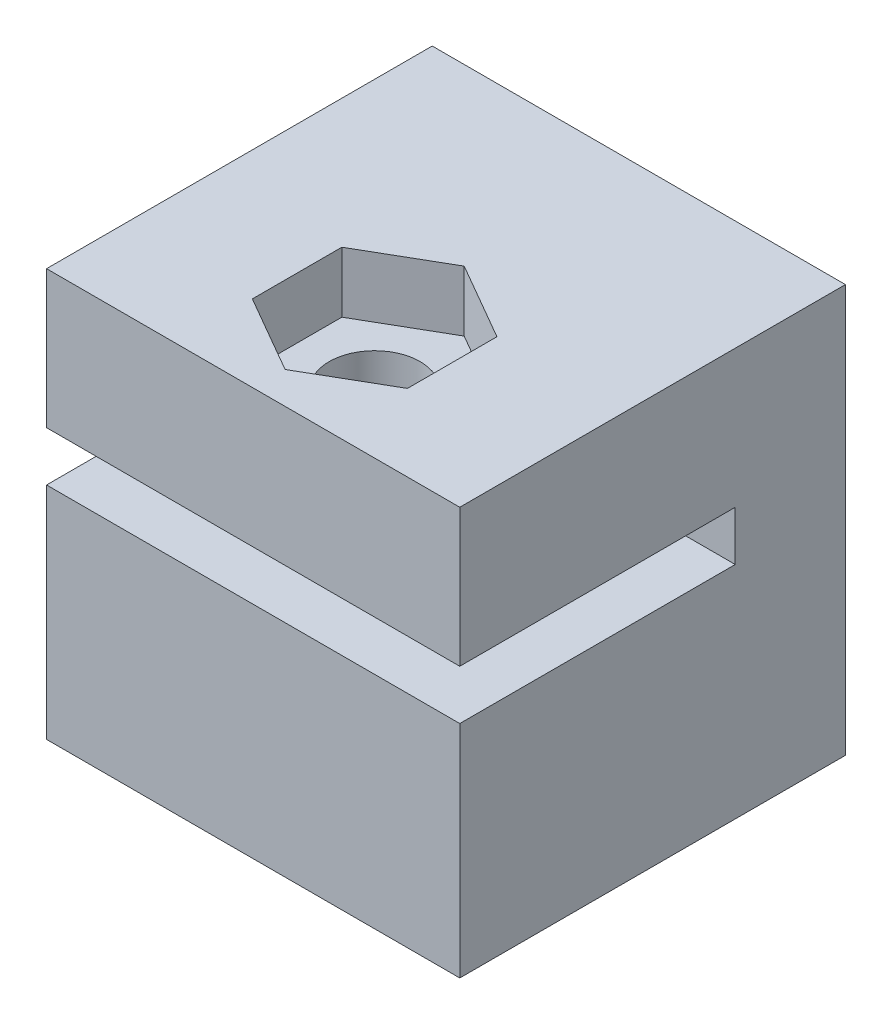
SolidWorks part; units mm, degrees
ref_plane "Front Plane" through (0, 0, 0) normal (0, 0, 1) x (1, 0, 0)
ref_plane "Top Plane" through (0, 0, 0) normal (0, 1, 0) x (1, 0, 0)
ref_plane "Right Plane" through (0, 0, 0) normal (1, 0, 0) x (0, 0, -1)
sketch "Sketch1" plane through (0, 0, 0) normal (0, 1, 0) x (1, 0, 0)
  line L1 (-7.5, 7) -> (7.5, 7)
  line L2 (-7.5, 7) -> (-7.5, -7)
  line L3 (-7.5, -7) -> (7.5, -7)
  line L4 (7.5, 7) -> (7.5, -7)
  line L5 (-7.5, 7) -> (7.5, -7) construction
  line L6 (-7.5, -7) -> (7.5, 7) construction
  point P0 (0, 0)
  dimension "D1" = 15
  dimension "D2" = 14
extrude "base" add sketch "Sketch1" along normal blind 8
sketch "Sketch3" plane through (0, 8, 0) normal (0, 1, 0) x (1, 0, 0)
  line L0 (-5.9962, -7) -> (5.9962, -7)
  line L1 (-7.5, -7) -> (7.5, -7) construction
  line L3 (-5.9962, -7) -> (5.9962, -7)
  line L4 (-5.9962, -7) -> (-5.9962, 1)
  line L5 (-5.9962, 1) -> (5.9962, 1)
  line L6 (5.9962, -7) -> (5.9962, 1)
  line L7 (-7.5, 7) -> (7.5, 7)
  line L8 (-7.5, 7) -> (-7.5, -7)
  line L9 (-7.5, -7) -> (7.5, -7)
  line L10 (7.5, 7) -> (7.5, -7)
  line L11 (-7.5, 7) -> (7.5, 7)
  line L12 (-7.5, 7) -> (-7.5, 3)
  line L13 (-7.5, 3) -> (7.5, 3)
  line L14 (7.5, 7) -> (7.5, 3)
  point P5 (0, -7)
  line M14 (7.5, 7) -> (-7.5, 7)
  line M15 (-7.5, 7) -> (-7.5, -7)
  dimension "D1" = 8
extrude "spacer" add sketch "Sketch3" along normal blind 1.8 contours L13 L5 L10 M15 M14 region at (0, 8, -5)
sketch "Sketch4" plane through (0, 9.8, 0) normal (0, 1, 0) x (1, 0, 0)
  line L1 (-7.5, 7) -> (7.5, 7)
  line L2 (-7.5, 7) -> (-7.5, -7)
  line L3 (-7.5, -7) -> (7.5, -7)
  line L4 (7.5, 7) -> (7.5, -7)
  dimension "D1" = 14
extrude "top" add sketch "Sketch4" along normal blind 5
sketch "Sketch5" plane through (0, 14.8, 0) normal (0, 1, 0) x (1, 0, 0)
  line L0 (-6.0022, -7) -> (6.0022, -7)
  line L1 (-7.5, -7) -> (7.5, -7) construction
  line L2 (0, 7) -> (0, -2.59)
  line L3 (-6.0022, -7) -> (6.0022, -7)
  line L4 (-6.0022, -7) -> (-6.0022, 3)
  line L5 (-6.0022, 3) -> (6.0022, 3)
  line L6 (6.0022, -7) -> (6.0022, 3)
  line L7 (7.5, 7) -> (-7.5, 7) construction
  circle A1 centre (0, -2.59) radius 1.65
  point P5 (0, -7)
  dimension "D1" = 3.3
  dimension "D3" = 9.59
extrude "bore" cut sketch "Sketch5" against normal through all contours A1
sketch "Sketch6" plane through (0, 14.8, 0) normal (0, 1, 0) x (1, 0, 0)
  line L7 (0, 0.66) -> (-2.8146, -0.965)
  line L8 (-2.8146, -0.965) -> (-2.8146, -4.215)
  line L9 (-2.8146, -4.215) -> (0, -5.84)
  line L10 (0, -5.84) -> (2.8146, -4.215)
  line L11 (2.8146, -4.215) -> (2.8146, -0.965)
  line L12 (2.8146, -0.965) -> (0, 0.66)
  circle A0 centre (0, -2.59) radius 2.8146 construction
  dimension "D1" = 6.5
extrude "nut" cut sketch "Sketch6" against normal blind 2.2 contours L7 L8 L9 L10 L11 L12
